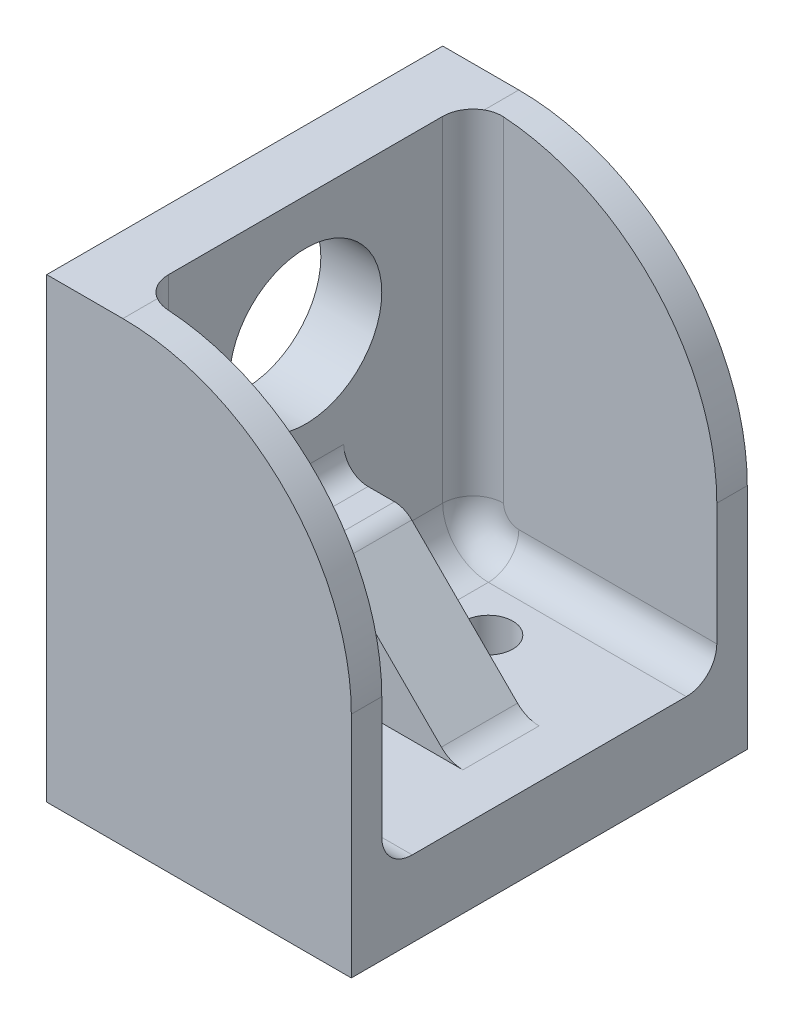
SolidWorks part; units mm, degrees
material "ABS"
ref_plane "前视基准面" through (0, 0, 0) normal (0, 0, 1) x (1, 0, 0)
ref_plane "上视基准面" through (0, 0, 0) normal (0, 1, 0) x (1, 0, 0)
ref_plane "右视基准面" through (0, 0, 0) normal (1, 0, 0) x (0, 0, -1)
sketch "草图1" plane through (0, 0, 0) normal (0, 0, 1) x (1, 0, 0)
  line L0 (0, 30) -> (0, 0)
  line L1 (0, 0) -> (20, 0)
  line L2 (2, 30) -> (2, 2)
  line L3 (2, 2) -> (20, 2)
  line L4 (0, 30) -> (2, 30)
  line L5 (20, 0) -> (20, 2)
  dimension "D1" = 30
  dimension "D2" = 20
  dimension "D3" = 2
extrude "凸台-拉伸1" add sketch "草图1" along normal blind 13 and the other way blind 13
sketch "草图2" plane through (2, 0, 0) normal (1, 0, 0) x (0, 0, -1)
  line L0 (13, 2) -> (-13, 2) construction
  circle A0 centre (0, 22) radius 5
  dimension "D1" = 10
  dimension "D2" = 20
extrude "切除-拉伸1" cut sketch "草图2" against normal through all
sketch "草图3" plane through (0, 2, 0) normal (0, 1, 0) x (1, 0, 0)
  line L0 (0, 0) -> (20, 0) construction
  line L1 (20, 13) -> (20, -13) construction
  circle A0 centre (10, 6) radius 1.6
  circle A1 centre (10, -6) radius 1.6
  point P8 (10, 0)
  dimension "D1" = 3.2
  dimension "D2" = 6
extrude "切除-拉伸2" cut sketch "草图3" against normal through all
sketch "草图4" plane through (0, 2, 0) normal (0, 1, 0) x (1, 0, 0)
  line L4 (2, 13) -> (2, -13)
  line L5 (2, -13) -> (20, -13)
  line L6 (20, -13) -> (20, 13)
  line L7 (20, 13) -> (2, 13)
  line L8 (2, 13) -> (2, -13)
  line L9 (2, -13) -> (20, -13)
  line L10 (20, -13) -> (20, 13)
  line L11 (20, 13) -> (2, 13)
  circle A0 centre (10, -6) radius 1.6 construction
  circle A1 centre (10, 6) radius 1.6 construction
  circle A2 centre (10, -6) radius 1.6
  circle A3 centre (10, 6) radius 1.6
  dimension "D1" = 0
extrude "凸台-拉伸2" add sketch "草图4" along normal blind 3
sketch "草图5" plane through (2, 0, 0) normal (1, 0, 0) x (0, 0, -1)
  line L4 (-13, 5) -> (13, 5)
  line L5 (13, 5) -> (13, 30)
  line L6 (13, 30) -> (-13, 30)
  line L7 (-13, 30) -> (-13, 5)
  line L8 (-13, 5) -> (13, 5)
  line L9 (13, 5) -> (13, 30)
  line L10 (13, 30) -> (-13, 30)
  line L11 (-13, 30) -> (-13, 5)
  circle A0 centre (0, 22) radius 5 construction
  circle A1 centre (0, 22) radius 5
  dimension "D1" = 0
extrude "凸台-拉伸3" add sketch "草图5" along normal blind 2
sketch "草图6" plane through (0, 5, 0) normal (0, 1, 0) x (1, 0, 0)
  line L0 (4, 13) -> (4, -13) construction
  line L1 (4, 2.5) -> (18, 2.5)
  line L2 (4, 2.5) -> (4, -2.5)
  line L3 (4, -2.5) -> (18, -2.5)
  line L4 (18, 2.5) -> (18, -2.5)
  line L5 (20, 13) -> (4, 13) construction
  line L6 (4, -13) -> (20, -13) construction
  dimension "D1" = 10.5
  dimension "D2" = 10.5
  dimension "D3" = 14
extrude "凸台-拉伸4" add sketch "草图6" along normal blind 8
chamfer "倒角1" distance 10 angle 45 1 edges at (18, 13, 0)
fillet "圆角1" radius 3 2 edges at (4, 5, -7.75) (4, 5, 7.75)
sketch "草图7" plane through (0, 5, 0) normal (0, 1, 0) x (1, 0, 0)
  line L0 (4, 13) -> (4, -13) construction
  line L1 (20, 13) -> (4, 13)
  line L2 (20, 13) -> (20, 11)
  line L3 (20, 11) -> (4, 11)
  line L4 (4, 13) -> (4, 11)
  line L5 (-1000, 0) -> (49000, 0) construction
  line L6 (20, -11) -> (4, -11)
  line L7 (4, -13) -> (4, -11)
  line L8 (20, -13) -> (4, -13)
  line L9 (20, -13) -> (20, -11)
  dimension "D1" = 2
extrude "凸台-拉伸5" add sketch "草图7" along normal up to surface (25 mm away) up to face at (2, 30, 0)
fillet "圆角2" radius 15 2 edges at (20, 30, 12) (20, 30, -12)
fillet "圆角3" radius 2 7 edges at (13.5, 5, 11) (4.8787, 5.8787, 11) (13.5, 5, -11) (4.8787, 5.8787, -11) (16, 5, 0) (4, 19, 11) (4, 19, -11)
fillet "圆角4" radius 1.6 2 edges at (4, 13, 0) (8, 13, 0)
